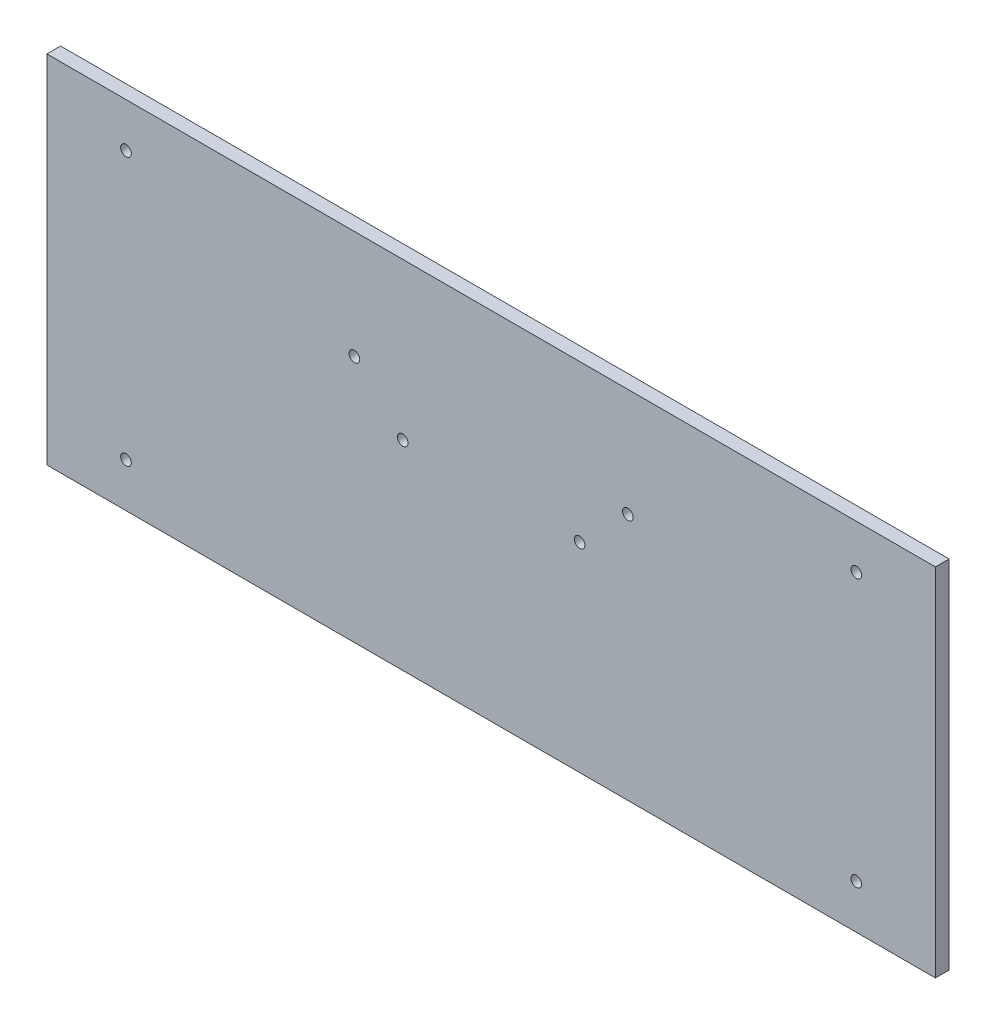
SolidWorks part; units mm, degrees
material "ABS"
ref_plane "Front Plane" through (0, 0, 0) normal (0, 0, 1) x (1, 0, 0)
ref_plane "Top Plane" through (0, 0, 0) normal (0, 1, 0) x (1, 0, 0)
ref_plane "Right Plane" through (0, 0, 0) normal (1, 0, 0) x (0, 0, -1)
sketch "Sketch1" plane through (0, 0, 0) normal (0, 0, 1) x (1, 0, 0)
  line L0 (0, 0) -> (0, 166.746) construction
  line L1 (146, -58.5) -> (-146, -58.5)
  line L2 (146, -58.5) -> (146, 58.5)
  line L3 (146, 58.5) -> (-146, 58.5)
  line L4 (-146, -58.5) -> (-146, 58.5)
  line L5 (146, -58.5) -> (-146, 58.5) construction
  line L6 (146, 58.5) -> (-146, -58.5) construction
  line L7 (0, 0) -> (-259.0657, 0) construction
  circle A0 centre (-120, 44) radius 1.75
  point P0 (0, 0)
  dimension "D5" = 3.5
  dimension "D1" = 292
  dimension "D2" = 117
  dimension "D3" = 44
  dimension "D4" = 120
extrude "Boss-Extrude1" add sketch "Sketch1" along normal blind 4.5 contours L4 L1 L2 L3 A0 | A0 region at (0.0338, -0.0124, 0) region at (-120, 44, 0)
extrude "Cut-Extrude1" cut sketch "Sketch1<3>" along normal up to next contours A0
sketch "Sketch1<3>" plane through (0, 0, 0) normal (0, 0, 1) x (1, 0, 0) same geometry as "Sketch1"
mirror "Mirror2" about plane through (0, 0, 0) normal (0, 1, 0) of "Cut-Extrude1"
mirror "Mirror3" about plane through (0, 0, 0) normal (1, 0, 0) of "Mirror2"
sketch "Sketch2" plane through (0, 0, 4.5) normal (0, 0, 1) x (1, 0, 0)
  line L0 (0, 0) -> (0, 58.5) construction
  line L1 (146, 58.5) -> (-146, 58.5) construction
  line L2 (22, 0) -> (-22, 0) construction
  line L3 (-22, 0) -> (-52, 30) construction
  line L4 (22, 0) -> (52, 30) construction
  circle A0 centre (-29.0711, 7.0711) radius 1.75
  circle A1 centre (-44.9289, 22.9289) radius 1.75
  circle A2 centre (44.9289, 22.9289) radius 1.75
  circle A3 centre (29.0711, 7.0711) radius 1.75
  dimension "D6" = 3.5
  dimension "D7" = 3.5
  dimension "D1" = 22
  dimension "D2" = 45
  dimension "D3" = 30
  dimension "D4" = 10
  dimension "D5" = 10
extrude "Cut-Extrude2" cut sketch "Sketch2" against normal up to next
